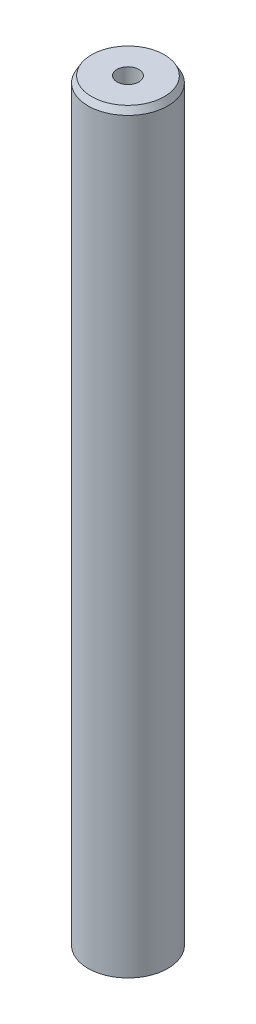
SolidWorks part; units mm, degrees
ref_plane "Front Plane" through (0, 0, 0) normal (0, 0, 1) x (1, 0, 0)
ref_plane "Top Plane" through (0, 0, 0) normal (0, 1, 0) x (1, 0, 0)
ref_plane "Right Plane" through (0, 0, 0) normal (1, 0, 0) x (0, 0, -1)
sketch "Sketch1" plane through (0, 0, 0) normal (0, 1, 0) x (1, 0, 0)
  circle A0 centre (0, 0) radius 5
  dimension "SHAFT_OD" = 10
extrude "Boss-Extrude1" add sketch "Sketch1" along normal blind 94.7807
sketch "Sketch2" plane through (0, 0, 0) normal (0, 1, 0) x (1, 0, 0)
  circle A0 centre (0, 0) radius 1.3694
  dimension "BORE_D" = 2.7388
extrude "Cut-Extrude1" cut sketch "Sketch2" along normal through all
chamfer "Chamfer1" distance 0.7791 angle 30 2 edges at (0, 94.7807, 5) (0, 0, 5) first distance on face at (0, 94.7807, 5) first distance on face at (0, 0, 1.3694)
